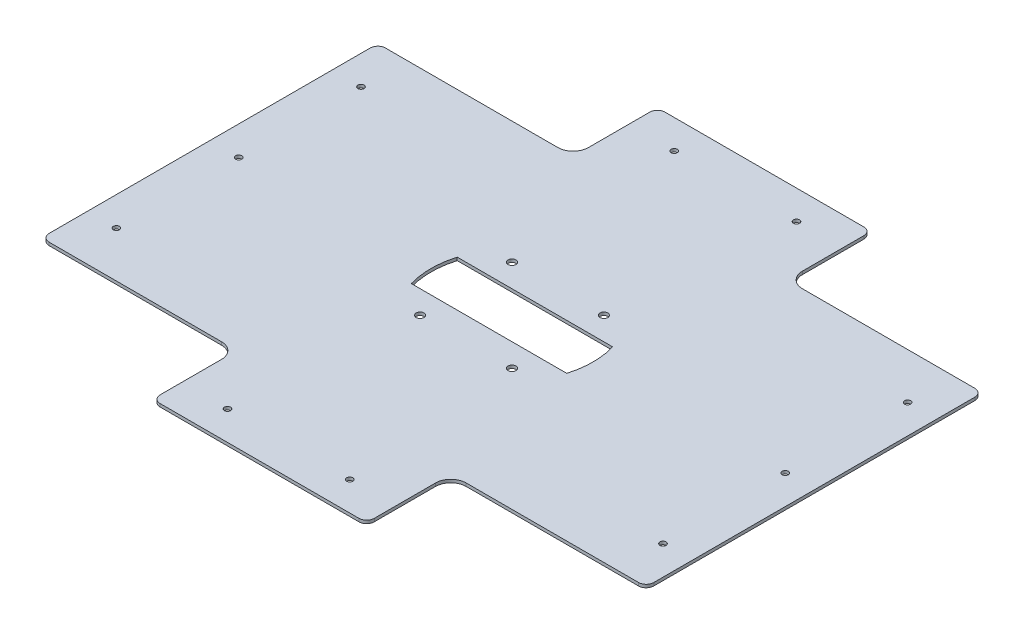
SolidWorks part; units mm, degrees
material "1060 Сплав"
ref_plane "Спереди" through (0, 0, 0) normal (0, 0, 1) x (1, 0, 0)
ref_plane "Сверху" through (0, 0, 0) normal (0, 1, 0) x (1, 0, 0)
ref_plane "Справа" through (0, 0, 0) normal (1, 0, 0) x (0, 0, -1)
sketch "Эскиз1" plane through (0, 0, 0) normal (0, 1, 0) x (1, 0, 0)
  line L1 (-65, -165.1043) -> (65, -165.1043)
  line L2 (-197.7687, -105) -> (-197.7687, 105)
  line L3 (-65, 165.1043) -> (65, 165.1043)
  line L4 (197.7687, -105) -> (197.7687, 105)
  line L18 (-284.5497, 0) -> (284.3305, 0) construction
  line L39 (-70, 120) -> (-70, 160.1043)
  line L40 (0, 262.7398) -> (0, -186.5795) construction
  line L41 (-192.7687, 110) -> (-80, 110)
  line L43 (-192.7687, -110) -> (-80, -110)
  line L44 (-70, -120) -> (-70, -160.1043)
  line L45 (70, 120) -> (70, 160.1043)
  line L46 (192.7687, 110) -> (80, 110)
  line L47 (192.7687, -110) -> (80, -110)
  line L48 (70, -120) -> (70, -160.1043)
  line L54 (160.9018, -110) -> (134.9018, -110)
  line L60 (160.9018, 110) -> (134.9018, 110)
  arc A0 (70, -120) -> (80, -110) centre (80, -120) cw
  arc A1 (70, 120) -> (80, 110) centre (80, 120) ccw
  arc A2 (-80, -110) -> (-70, -120) centre (-80, -120) cw
  arc A3 (-70, 120) -> (-80, 110) centre (-80, 120) cw
  arc A4 (192.7687, -110) -> (197.7687, -105) centre (192.7687, -105) ccw
  arc A5 (70, -160.1043) -> (65, -165.1043) centre (65, -160.1043) cw
  arc A6 (-70, -160.1043) -> (-65, -165.1043) centre (-65, -160.1043) ccw
  arc A7 (-192.7687, -110) -> (-197.7687, -105) centre (-192.7687, -105) cw
  arc A8 (-192.7687, 110) -> (-197.7687, 105) centre (-192.7687, 105) ccw
  arc A9 (197.7687, 105) -> (192.7687, 110) centre (192.7687, 105) ccw
  arc A10 (70, 160.1043) -> (65, 165.1043) centre (65, 160.1043) ccw
  arc A11 (-70, 160.1043) -> (-65, 165.1043) centre (-65, 160.1043) cw
  circle A22 centre (178.7687, 0) radius 2
  circle A23 centre (178.7687, 80) radius 2
  circle A24 centre (178.7687, -80) radius 2
  circle A25 centre (-178.7687, -80) radius 2
  circle A26 centre (-178.7687, 0) radius 2
  circle A27 centre (-178.7687, 80) radius 2
  circle A28 centre (40, 146.1043) radius 2
  circle A29 centre (-40, 146.1043) radius 2
  circle A30 centre (-40, -146.1043) radius 2
  circle A31 centre (40, -146.1043) radius 2
  point P0 (0, 0)
  point P3 (70, -110)
  point P8 (197.7687, 0)
  point P18 (-147.9018, 110)
  point P46 (70, 110)
  point P52 (-70, -110)
  point P55 (-70, 110)
  point P56 (-147.9018, 0)
  point P77 (197.7687, -110)
  point P80 (70, -165.1043)
  point P83 (-70, -165.1043)
  point P86 (-197.7687, -110)
  point P89 (-197.7687, 110)
  point P92 (197.7687, 110)
  point P95 (70, 165.1043)
  point P98 (-70, 165.1043)
  dimension "D2" = 4
  dimension "D6" = 10
  dimension "D11" = 40
  dimension "D12" = 330.2086
  dimension "D4" = 5
  dimension "D1" = 4
  dimension "D8" = 4
  dimension "D3" = 19
  dimension "D5" = 80
  dimension "D7" = 19
  dimension "D9" = 140
  dimension "D10" = 19
  dimension "D13" = 395.5373
sketch "Эскиз2" plane through (0, 0, 0) normal (0, 1, 0) x (1, 0, 0)
  line L0 (-162.9105, 114) -> (-136.9105, 114)
  line L1 (-162.9105, 114) -> (-162.9105, 0)
  line L2 (-162.9105, 0) -> (-136.9105, 0)
  line L3 (-136.9105, 114) -> (-136.9105, 0)
  line L4 (-149.9105, -192.6295) -> (-149.9105, 209.9923) construction
  line L5 (-162.9105, 0) -> (-136.9105, 0)
  line L6 (-162.9105, 0) -> (-162.9105, -114)
  line L7 (-162.9105, -114) -> (-136.9105, -114)
  line L8 (-136.9105, 0) -> (-136.9105, -114)
  line L9 (-99.9105, -123.5568) -> (-199.9105, -123.5568)
  line L10 (-99.9105, 163.4996) -> (-199.9105, 163.4996)
  line L11 (-99.9105, 163.4996) -> (-99.9105, 123.4996)
  line L12 (-99.9105, 123.4996) -> (-199.9105, 123.4996)
  line L13 (-199.9105, 163.4996) -> (-199.9105, 123.4996)
  line L14 (-199.9105, -163.5568) -> (-199.9105, -123.5568)
  line L15 (-99.9105, -163.5568) -> (-199.9105, -163.5568)
  line L16 (-99.9105, -163.5568) -> (-99.9105, -123.5568)
  line L17 (-284.5497, 0) -> (284.3305, 0) construction
  point P11 (-149.9105, 0)
  point P12 (-149.9105, 0)
sketch "Эскиз3" plane through (0, 0, 0) normal (0, 1, 0) x (1, 0, 0)
  line L0 (-89.8176, -177.9027) -> (70.2405, -177.9027)
  line L1 (-209.7886, -106.9112) -> (-209.7886, 106.8353)
  line L2 (-80.029, 172.0973) -> (50.2405, 172.0973)
  line L3 (170.2114, -106.9112) -> (170.2114, 103.9123)
  line L4 (-87.1938, 124.0033) -> (-87.1938, 164.9326)
  line L5 (-202.6239, 114) -> (-97.1971, 114)
  line L6 (-202.6239, -114.076) -> (-106.9857, -114.076)
  line L7 (-96.9823, -124.0793) -> (-96.9823, -170.738)
  line L8 (57.4052, 121.0803) -> (57.4052, 164.9326)
  line L9 (163.0467, 111.077) -> (67.4085, 111.077)
  line L10 (163.0467, -114.076) -> (87.4085, -114.076)
  line L11 (77.4052, -124.0793) -> (77.4052, -170.738)
  line L13 (-162.9105, 114) -> (-136.9105, 114) construction
  arc A0 (77.4052, -124.0793) -> (87.4085, -114.076) centre (87.4085, -124.0793) cw
  arc A1 (57.4052, 121.0803) -> (67.4085, 111.077) centre (67.4085, 121.0803) ccw
  arc A2 (-106.9857, -114.076) -> (-96.9823, -124.0793) centre (-106.9857, -124.0793) cw
  arc A3 (-87.1938, 124.0033) -> (-97.1971, 114) centre (-97.1971, 124.0033) cw
  arc A4 (-80.029, 172.0973) -> (-87.1938, 164.9326) centre (-80.029, 164.9326) ccw
  arc A5 (50.2405, 172.0973) -> (57.4052, 164.9326) centre (50.2405, 164.9326) cw
  arc A6 (170.2114, 103.9123) -> (163.0467, 111.077) centre (163.0467, 103.9123) ccw
  arc A7 (170.2114, -106.9112) -> (163.0467, -114.076) centre (163.0467, -106.9112) cw
  arc A8 (70.2405, -177.9027) -> (77.4052, -170.738) centre (70.2405, -170.738) ccw
  arc A9 (-89.8176, -177.9027) -> (-96.9823, -170.738) centre (-89.8176, -170.738) cw
  arc A10 (-209.7886, -106.9112) -> (-202.6239, -114.076) centre (-202.6239, -106.9112) ccw
  arc A11 (-209.7886, 106.8353) -> (-202.6239, 114) centre (-202.6239, 106.8353) cw
  point P36 (115.2276, 111.077)
  point P39 (-149.9105, 114)
  point P42 (-149.9105, 114)
  dimension "D3" = 10.0033
  dimension "D4" = 7.1647
  dimension "D1" = 380
  dimension "D2" = 350
  dimension "D5" = 112.8062
  dimension "D6" = 63.8267
  dimension "D7" = 61.0203
extrude "Бобышка-Вытянуть1" add sketch "Эскиз1" along normal blind 2 separate body contours A11 L39 A3 L41 L43 A2 L44 A6 L1 A5 L48 A0 L47 L46 A1 L45 A10 L3 | L4 A9 L46 L47 A4 | L46 | L47 | L41 A8 L2 A7 L43 region at (0, 0, 0)
sketch "Эскиз5" plane through (0, 0, 0) normal (0, -1, 0) x (1, 0, 0)
  line L0 (50.8331, -15) -> (-50.8331, -15)
  line L7 (50.8331, 15) -> (-50.8331, 15)
  arc A0 (50.8331, -15) -> (50.8331, 15) centre (0, 0) ccw
  arc A1 (-50.8331, 15) -> (-50.8331, -15) centre (0, 0) ccw
  point P0 (0, 0)
  dimension "D2" = 101.6661
  dimension "D3" = 101.6661
  dimension "D1" = 30
extrude "Вырез-Вытянуть2" cut sketch "Эскиз5" against normal through all
hole_wizard "Сверло под метчик  спиральное M51" positions "Эскиз6" profile "Эскиз7" hole size "M5x0.8" standard "DIN"
sketch "Эскиз6" plane through (0, 2, 0) normal (0, 1, 0) x (1, 0, 0)
  line L0 (0, 0) -> (0, 24.7801) construction
  line L1 (30.052, 30.052) -> (0, 0) construction
  circle A0 centre (0, 0) radius 42.5
  point P15 (30.052, 30.052)
  dimension "D1" = 85
  dimension "D2" = 45
sketch "Эскиз7" plane through (30.052, 2, -30.052) normal (1, 0, 0) x (0, 0, 1)
  line L0 (0, 0) -> (0, 9.5622)
  line L1 (0, 9.5622) -> (2.6, 8)
  line L2 (2.6, 8) -> (2.6, 0)
  line L5 (2.6, 0) -> (0, 0)
  line L10 (0, 9.5622) -> (-2.6, 8) construction
  line L11 (0, -6.35) -> (0, 107.95) construction
  dimension "Диаметр отверстия" = 5.2
  dimension "Глубина отверстия" = 8
  dimension "Угол заточки сверла" = 118
pattern_circular "Круговой массив1" count 4 over 360 about axis through (0, 2, 0) along (0, -1, 0) of "Сверло под метчик  спиральное M51"
